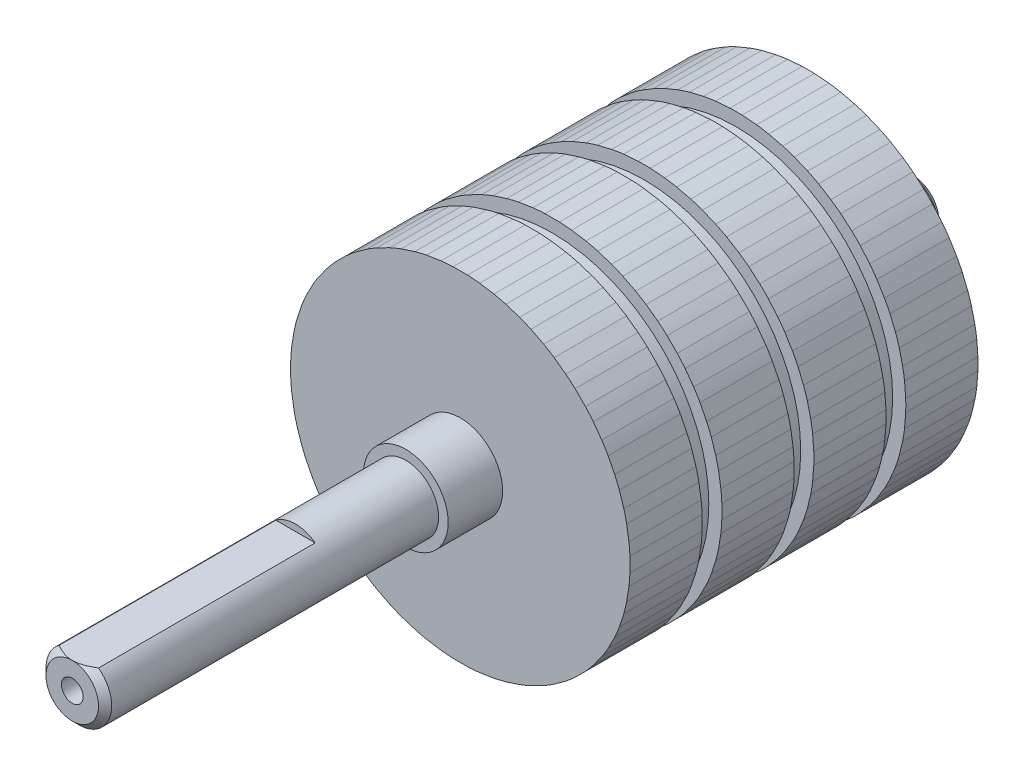
SolidWorks part; units mm, degrees
material "AISI Type A2 Tool Steel"
ref_plane "Front" through (0, 0, 0) normal (0, 0, 1) x (1, 0, 0)
ref_plane "Top" through (0, 0, 0) normal (0, 1, 0) x (1, 0, 0)
ref_plane "Right" through (0, 0, 0) normal (1, 0, 0) x (0, 0, -1)
sketch "Sketch1" plane through (0, 0, 0) normal (1, 0, 0) x (0, 0, -1)
  line L0 (-34.7383, 0) -> (0, 0) construction
  line L1 (0, 0) -> (0, 20.5789) construction
  line L2 (-27.9, -0.825) -> (-27.9, -2)
  line L3 (1.65, -12.925) -> (2.65, -11.925)
  line L4 (2.65, -11.925) -> (6.15, -11.925)
  line L5 (-27.9, -2) -> (-27.4, -2.5)
  line L6 (13.15, -11.925) -> (14.15, -12.925)
  line L7 (-27.4, -2.5) -> (-2.5, -2.5)
  line L8 (15.65, -12.925) -> (16.65, -11.925)
  line L9 (-2.5, -2.5) -> (-2.5, -3.225)
  line L10 (-2.5, -3.225) -> (1.65, -3.225)
  line L11 (1.65, -3.225) -> (1.65, -12.925)
  line L12 (1.65, -12.925) -> (14.15, -12.925)
  line L13 (14.15, -12.925) -> (14.15, -11.925)
  line L14 (16.65, -11.925) -> (20.15, -11.925)
  line L15 (14.15, -11.925) -> (15.65, -11.925)
  line L16 (27.15, -11.925) -> (28.15, -12.925)
  line L17 (15.65, -11.925) -> (15.65, -12.925)
  line L18 (15.65, -12.925) -> (28.15, -12.925)
  line L19 (21.15, -12.925) -> (21.15, -11.925)
  line L20 (28.15, -12.925) -> (28.15, -3.225)
  line L21 (28.15, -3.225) -> (31.6, -3.225)
  line L22 (21.15, -11.925) -> (22.65, -11.925)
  line L23 (31.6, -3.225) -> (31.6, -2.5)
  line L24 (22.65, -11.925) -> (22.65, -12.925)
  line L25 (31.6, -2.5) -> (35.6, -2.5)
  line L26 (22.65, -12.925) -> (23.65, -11.925)
  line L27 (35.6, -2.5) -> (36.1, -2)
  line L28 (21.15, -12.925) -> (20.15, -11.925)
  line L29 (36.1, -2) -> (36.1, -0.875)
  line L30 (21.15, -11.925) -> (22.65, -11.925)
  line L31 (36.1, -0.875) -> (34.6, -0.875)
  line L32 (23.65, -11.925) -> (27.15, -11.925)
  line L33 (34.6, -0.875) -> (34.6, 0)
  line L34 (34.6, 0) -> (-26.4, 0)
  line L35 (7.15, -12.925) -> (7.15, -11.925)
  line L36 (-26.4, 0) -> (-26.4, -0.825)
  line L37 (-26.4, -0.825) -> (-27.9, -0.825)
  line L38 (8.65, -11.925) -> (8.65, -12.925)
  line L39 (8.65, -12.925) -> (9.65, -11.925)
  line L40 (7.15, -12.925) -> (6.15, -11.925)
  line L41 (7.15, -11.925) -> (8.65, -11.925)
  line L42 (9.65, -11.925) -> (13.15, -11.925)
  dimension "D1" = 5
  dimension "D2" = 25.85
  dimension "D3" = 23.85
  dimension "D4" = 6.45
  dimension "D5" = 64
  dimension "D6" = 4.5
  dimension "D7" = 26.5
  dimension "D8" = 1.65
  dimension "D9" = 4.15
  dimension "D10" = 3.45
  dimension "D11" = 1.5
  dimension "D12" = 1.75
  dimension "D13" = 0.5
  dimension "D14" = 45
  dimension "D15" = 1.5
  dimension "D16" = 1.65
  dimension "D17" = 1.5
  dimension "D18" = 45
revolve "Revolve1" add sketch "Sketch1" angle 360 about L0 region at (0, -4.9572, -10.7971)
sketch "Sketch2" plane through (0, 0, -1.65) normal (0, 0, 1) x (1, 0, 0)
  line L0 (0, 0) -> (0, 12.9133) construction
  line L1 (4.957, 11.9672) -> (3.0239, 12.5953)
  line L2 (3.0239, 12.5953) -> (1.0163, 12.9133)
  line L3 (1.0163, 12.9133) -> (-1.0163, 12.9133)
  line L4 (-1.0163, 12.9133) -> (-3.0239, 12.5953)
  line L5 (-3.0239, 12.5953) -> (-4.957, 11.9672)
  line L6 (-4.957, 11.9672) -> (-6.768, 11.0444)
  line L7 (-6.768, 11.0444) -> (-8.4124, 9.8497)
  line L8 (-8.4124, 9.8497) -> (-9.8497, 8.4124)
  line L9 (-9.8497, 8.4124) -> (-11.0444, 6.768)
  line L10 (-11.0444, 6.768) -> (-11.9672, 4.957)
  line L11 (-11.9672, 4.957) -> (-12.5953, 3.0239)
  line L12 (-12.5953, 3.0239) -> (-12.9133, 1.0163)
  line L13 (-12.9133, 1.0163) -> (-12.9133, -1.0163)
  line L14 (-12.9133, -1.0163) -> (-12.5953, -3.0239)
  line L15 (-12.5953, -3.0239) -> (-11.9672, -4.957)
  line L16 (-11.9672, -4.957) -> (-11.0444, -6.768)
  line L17 (-11.0444, -6.768) -> (-9.8497, -8.4124)
  line L18 (-9.8497, -8.4124) -> (-8.4124, -9.8497)
  line L19 (-8.4124, -9.8497) -> (-6.768, -11.0444)
  line L20 (-6.768, -11.0444) -> (-4.957, -11.9672)
  line L21 (-4.957, -11.9672) -> (-3.0239, -12.5953)
  line L22 (-3.0239, -12.5953) -> (-1.0163, -12.9133)
  line L23 (-1.0163, -12.9133) -> (1.0163, -12.9133)
  line L24 (1.0163, -12.9133) -> (3.0239, -12.5953)
  line L25 (3.0239, -12.5953) -> (4.957, -11.9672)
  line L26 (4.957, -11.9672) -> (6.768, -11.0444)
  line L27 (6.768, -11.0444) -> (8.4124, -9.8497)
  line L28 (8.4124, -9.8497) -> (9.8497, -8.4124)
  line L29 (9.8497, -8.4124) -> (11.0444, -6.768)
  line L30 (11.0444, -6.768) -> (11.9672, -4.957)
  line L31 (11.9672, -4.957) -> (12.5953, -3.0239)
  line L32 (12.5953, -3.0239) -> (12.9133, -1.0163)
  line L33 (12.9133, -1.0163) -> (12.9133, 1.0163)
  line L34 (12.9133, 1.0163) -> (12.5953, 3.0239)
  line L35 (12.5953, 3.0239) -> (11.9672, 4.957)
  line L36 (11.9672, 4.957) -> (11.0444, 6.768)
  line L37 (11.0444, 6.768) -> (9.8497, 8.4124)
  line L38 (9.8497, 8.4124) -> (8.4124, 9.8497)
  line L39 (8.4124, 9.8497) -> (6.768, 11.0444)
  line L40 (6.768, 11.0444) -> (4.957, 11.9672)
  circle A0 centre (0, 0) radius 12.9133 construction
  circle A1 centre (0, 0) radius 12.925 construction
  circle A3 centre (0, 0) radius 12.925 construction
  point P45 (0.55, 12.9133)
  dimension "D1" = 0.55
revolve "Revolve2" add sketch "Sketch1<3>" angle 360 about L0 region at (0, -12.462, -4.4) region at (0, -12.462, -11.4) region at (0, -12.462, -25.4) region at (0, -12.462, -18.4)
sketch "Sketch1<3>" plane through (0, 0, 0) normal (1, 0, 0) x (0, 0, -1) same geometry as "Sketch1"
extrude "Cut-Extrude1" cut sketch "Sketch2" against normal up to surface (12.5 mm away) flip side to cut up to face at (11.925, 0, -14.15)
sketch "Sketch3" plane through (0, 0, -28.15) normal (0, 0, -1) x (-1, 0, 0)
  line L0 (0, 0) -> (1.0132, 12.8735) construction
  line L1 (0, 12.9532) -> (-2.0263, 12.7937)
  line L2 (-2.0263, 12.7937) -> (-4.0028, 12.3192)
  line L3 (-4.0028, 12.3192) -> (-5.8806, 11.5414)
  line L4 (-5.8806, 11.5414) -> (-7.6137, 10.4794)
  line L5 (-7.6137, 10.4794) -> (-9.1593, 9.1593)
  line L6 (-9.1593, 9.1593) -> (-10.4794, 7.6137)
  line L7 (-10.4794, 7.6137) -> (-11.5414, 5.8806)
  line L8 (-11.5414, 5.8806) -> (-12.3192, 4.0028)
  line L9 (-12.3192, 4.0028) -> (-12.7937, 2.0263)
  line L10 (-12.7937, 2.0263) -> (-12.9532, 0)
  line L11 (-12.9532, 0) -> (-12.7937, -2.0263)
  line L12 (-12.7937, -2.0263) -> (-12.3192, -4.0028)
  line L13 (-12.3192, -4.0028) -> (-11.5414, -5.8806)
  line L14 (-11.5414, -5.8806) -> (-10.4794, -7.6137)
  line L15 (-10.4794, -7.6137) -> (-9.1593, -9.1593)
  line L16 (-9.1593, -9.1593) -> (-7.6137, -10.4794)
  line L17 (-7.6137, -10.4794) -> (-5.8806, -11.5414)
  line L18 (-5.8806, -11.5414) -> (-4.0028, -12.3192)
  line L19 (-4.0028, -12.3192) -> (-2.0263, -12.7937)
  line L20 (-2.0263, -12.7937) -> (0, -12.9532)
  line L21 (0, -12.9532) -> (2.0263, -12.7937)
  line L22 (2.0263, -12.7937) -> (4.0028, -12.3192)
  line L23 (4.0028, -12.3192) -> (5.8806, -11.5414)
  line L24 (5.8806, -11.5414) -> (7.6137, -10.4794)
  line L25 (7.6137, -10.4794) -> (9.1593, -9.1593)
  line L26 (9.1593, -9.1593) -> (10.4794, -7.6137)
  line L27 (10.4794, -7.6137) -> (11.5414, -5.8806)
  line L28 (11.5414, -5.8806) -> (12.3192, -4.0028)
  line L29 (12.3192, -4.0028) -> (12.7937, -2.0263)
  line L30 (12.7937, -2.0263) -> (12.9532, 0)
  line L31 (12.9532, 0) -> (12.7937, 2.0263)
  line L32 (12.7937, 2.0263) -> (12.3192, 4.0028)
  line L33 (12.3192, 4.0028) -> (11.5414, 5.8806)
  line L34 (11.5414, 5.8806) -> (10.4794, 7.6137)
  line L35 (10.4794, 7.6137) -> (9.1593, 9.1593)
  line L36 (9.1593, 9.1593) -> (7.6137, 10.4794)
  line L37 (7.6137, 10.4794) -> (5.8806, 11.5414)
  line L38 (5.8806, 11.5414) -> (4.0028, 12.3192)
  line L39 (4.0028, 12.3192) -> (2.0263, 12.7937)
  line L40 (2.0263, 12.7937) -> (0, 12.9532)
  circle A0 centre (0, 0) radius 12.9133 construction
  circle A2 centre (0, 0) radius 12.925 construction
  circle A3 centre (0, 0) radius 12.925 construction
  point P45 (1.5615, 12.8303)
  dimension "D1" = 0.55
extrude "Cut-Extrude2" cut sketch "Sketch3" against normal up to surface (12.5 mm away) flip side to cut up to face at (12.925, 0, -15.65)
sketch "Sketch4" plane through (0, 0, 27.9) normal (0, 0, 1) x (1, 0, 0)
  line L0 (-5.2183, -2.5) -> (10.7778, -2.5) construction
  line L1 (-2.5, 3) -> (2.5, 3)
  line L2 (-2.5, 3) -> (-2.5, 2)
  line L3 (-2.5, 2) -> (2.5, 2)
  line L4 (2.5, 3) -> (2.5, 2)
  line L5 (0, 0) -> (0, 6.0314) construction
  circle A0 centre (0, 0) radius 2.5 construction
  circle A1 centre (0, 0) radius 2.5 construction
  dimension "D1" = 4.5
  dimension "D2" = 1
extrude "Cut-Extrude3" cut sketch "Sketch4" against normal blind 17
